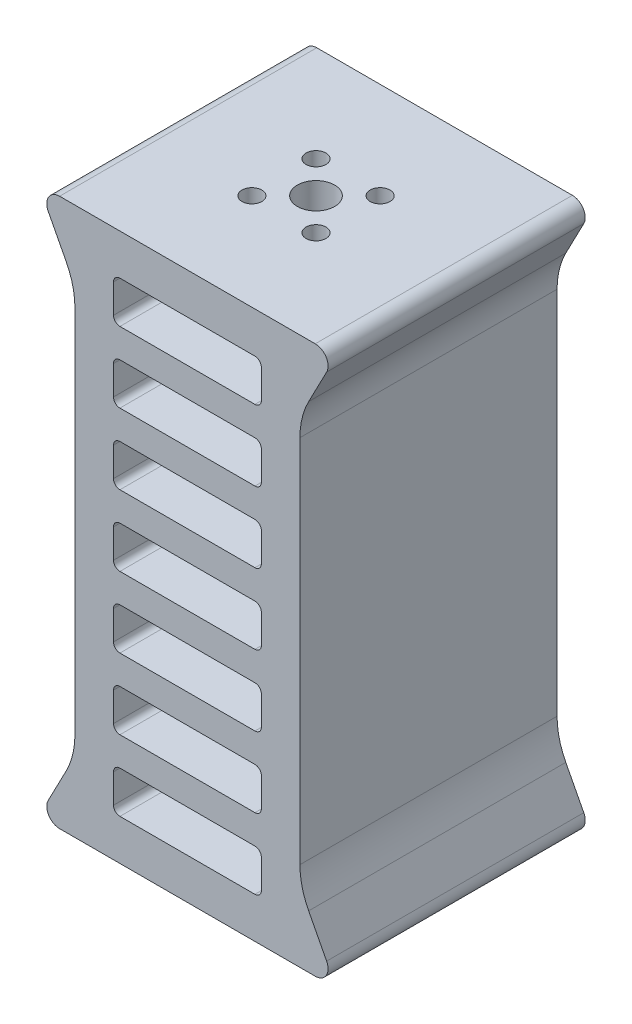
SolidWorks part; units mm, degrees
ref_plane "Front Plane" through (0, 0, 0) normal (0, 0, 1) x (1, 0, 0)
ref_plane "Top Plane" through (0, 0, 0) normal (0, 1, 0) x (1, 0, 0)
ref_plane "Right Plane" through (0, 0, 0) normal (1, 0, 0) x (0, 0, -1)
sketch "Sketch1" plane through (0, 0, 0) normal (0, 0, 1) x (1, 0, 0)
  line L1 (-15.5616, 7.5568) -> (19.4384, 7.5568)
  line L2 (-15.5616, 7.5568) -> (-15.5616, -77.6432)
  line L3 (-15.5616, -77.6432) -> (19.4384, -77.6432)
  line L4 (19.4384, 7.5568) -> (19.4384, -77.6432)
extrude "Boss-Extrude1" add sketch "Sketch1" along normal blind 20 and the other way blind 20
sketch "Sketch2" plane through (0, 0, 20) normal (0, 0, 1) x (1, 0, 0)
  line L0 (-9.5616, -10.7932) -> (-9.5616, -15.2932)
  line L1 (-8.5616, -9.7932) -> (12.4384, -9.7932)
  line L2 (13.4384, -10.7932) -> (13.4384, -15.2932)
  line L3 (-8.5616, -16.2932) -> (12.4384, -16.2932)
  line L4 (-9.5616, -21.7932) -> (-9.5616, -26.2932)
  line L5 (-8.5616, 1.2068) -> (12.4384, 1.2068)
  line L6 (-9.5616, 0.2068) -> (-9.5616, -4.2932)
  line L7 (-8.5616, -5.2932) -> (12.4384, -5.2932)
  line L16 (13.4384, 0.2068) -> (13.4384, -4.2932)
  line L17 (-8.5616, -20.7932) -> (12.4384, -20.7932)
  line L18 (13.4384, -21.7932) -> (13.4384, -26.2932)
  line L19 (-8.5616, -27.2932) -> (12.4384, -27.2932)
  line L20 (-9.5616, -32.7932) -> (-9.5616, -37.2932)
  line L21 (-8.5616, -31.7932) -> (12.4384, -31.7932)
  line L22 (13.4384, -32.7932) -> (13.4384, -37.2932)
  line L23 (-8.5616, -38.2932) -> (12.4384, -38.2932)
  line L24 (-9.5616, -43.7932) -> (-9.5616, -48.2932)
  line L25 (-8.5616, -42.7932) -> (12.4384, -42.7932)
  line L26 (13.4384, -43.7932) -> (13.4384, -48.2932)
  line L27 (-8.5616, -49.2932) -> (12.4384, -49.2932)
  line L28 (-9.5616, -54.7932) -> (-9.5616, -59.2932)
  line L29 (-8.5616, -53.7932) -> (12.4384, -53.7932)
  line L30 (13.4384, -54.7932) -> (13.4384, -59.2932)
  line L31 (-8.5616, -60.2932) -> (12.4384, -60.2932)
  line L32 (-9.5616, -65.7932) -> (-9.5616, -70.2932)
  line L33 (-8.5616, -64.7932) -> (12.4384, -64.7932)
  line L34 (13.4384, -65.7932) -> (13.4384, -70.2932)
  line L35 (-8.5616, -71.2932) -> (12.4384, -71.2932)
  arc A0 (-9.5616, -70.2932) -> (-8.5616, -71.2932) centre (-8.5616, -70.2932) ccw
  arc A1 (13.4384, -70.2932) -> (12.4384, -71.2932) centre (12.4384, -70.2932) cw
  arc A2 (12.4384, -64.7932) -> (13.4384, -65.7932) centre (12.4384, -65.7932) cw
  arc A3 (13.4384, -59.2932) -> (12.4384, -60.2932) centre (12.4384, -59.2932) cw
  arc A4 (-9.5616, -59.2932) -> (-8.5616, -60.2932) centre (-8.5616, -59.2932) ccw
  arc A5 (-9.5616, -65.7932) -> (-8.5616, -64.7932) centre (-8.5616, -65.7932) cw
  arc A6 (-9.5616, -54.7932) -> (-8.5616, -53.7932) centre (-8.5616, -54.7932) cw
  arc A7 (12.4384, -53.7932) -> (13.4384, -54.7932) centre (12.4384, -54.7932) cw
  arc A8 (13.4384, -48.2932) -> (12.4384, -49.2932) centre (12.4384, -48.2932) cw
  arc A9 (-9.5616, -48.2932) -> (-8.5616, -49.2932) centre (-8.5616, -48.2932) ccw
  arc A10 (-9.5616, -43.7932) -> (-8.5616, -42.7932) centre (-8.5616, -43.7932) cw
  arc A11 (12.4384, -42.7932) -> (13.4384, -43.7932) centre (12.4384, -43.7932) cw
  arc A12 (12.4384, -31.7932) -> (13.4384, -32.7932) centre (12.4384, -32.7932) cw
  arc A13 (13.4384, -37.2932) -> (12.4384, -38.2932) centre (12.4384, -37.2932) cw
  arc A14 (-9.5616, -37.2932) -> (-8.5616, -38.2932) centre (-8.5616, -37.2932) ccw
  arc A15 (-9.5616, -32.7932) -> (-8.5616, -31.7932) centre (-8.5616, -32.7932) cw
  arc A16 (-9.5616, -21.7932) -> (-8.5616, -20.7932) centre (-8.5616, -21.7932) cw
  arc A17 (-9.5616, -26.2932) -> (-8.5616, -27.2932) centre (-8.5616, -26.2932) ccw
  arc A18 (13.4384, -26.2932) -> (12.4384, -27.2932) centre (12.4384, -26.2932) cw
  arc A19 (12.4384, -20.7932) -> (13.4384, -21.7932) centre (12.4384, -21.7932) cw
  arc A20 (12.4384, -9.7932) -> (13.4384, -10.7932) centre (12.4384, -10.7932) cw
  arc A21 (13.4384, -15.2932) -> (12.4384, -16.2932) centre (12.4384, -15.2932) cw
  arc A22 (-9.5616, -15.2932) -> (-8.5616, -16.2932) centre (-8.5616, -15.2932) ccw
  arc A23 (-9.5616, -10.7932) -> (-8.5616, -9.7932) centre (-8.5616, -10.7932) cw
  arc A24 (12.4384, 1.2068) -> (13.4384, 0.2068) centre (12.4384, 0.2068) cw
  arc A25 (12.4384, -5.2932) -> (13.4384, -4.2932) centre (12.4384, -4.2932) ccw
  arc A26 (-9.5616, -4.2932) -> (-8.5616, -5.2932) centre (-8.5616, -4.2932) ccw
  arc A27 (-8.5616, 1.2068) -> (-9.5616, 0.2068) centre (-8.5616, 0.2068) ccw
  dimension "D1" = 1
  dimension "D2" = 7
extrude "Cut-Extrude2" cut sketch "Sketch2" against normal up to next
ref_plane "Plane1" through (0, 0, 6) normal (0, 0, 1) x (1, 0, 0)
sketch "Sketch4" plane through (-15.5616, 0, 0) normal (-1, 0, 0) x (0, 0, 1)
  line L0 (20, 7.5568) -> (20, -77.6432) construction
  point P0 (20, -35.0432)
ref_plane "Plane2" through (0, -35.0432, 0) normal (0, 1, 0) x (1, 0, 0)
sketch "Sketch5" plane through (0, 7.5568, 0) normal (0, 1, 0) x (1, 0, 0)
  circle A0 centre (-3.0467, 4.9851) radius 1.55
  circle A1 centre (1.9384, 0) radius 2.9
  circle A2 centre (6.9235, 4.9851) radius 1.55
  circle A3 centre (6.9235, -4.9851) radius 1.55
  circle A4 centre (-3.0467, -4.9851) radius 1.55
  point P9 (1.9384, 0)
  dimension "D2" = 3.1
  dimension "D1" = 4
extrude "Cut-Extrude3" cut sketch "Sketch5" against normal blind 8
sketch "Sketch6" plane through (0, 0, 20) normal (0, 0, 1) x (1, 0, 0)
  line L0 (-15.5616, 7.5568) -> (-15.5616, -77.6432) construction
  point P0 (-15.5616, -35.0432)
ref_plane "Plane3" through (0, -35.0432, 0) normal (0, 1, 0) x (1, 0, 0)
mirror "Mirror3" about plane through (0, -35.0432, 0) normal (0, 1, 0) of "Cut-Extrude3"
sketch "Sketch7" plane through (0, 0, -20) normal (0, 0, -1) x (-1, 0, 0)
  line L0 (-19.4384, 7.5568) -> (-21.8183, 7.5568)
  line L1 (-23.5923, 4.6332) -> (-20.7946, -0.7405)
  line L2 (-19.4384, -77.6432) -> (-19.4384, 7.5568) construction
  line L3 (-19.4384, -6.282) -> (-19.4384, 7.5568)
  line L4 (15.5616, -77.6432) -> (17.9415, -77.6432)
  line L7 (-19.4384, -63.8043) -> (-19.4384, -77.6432)
  line L8 (-23.5923, -74.7196) -> (-20.7946, -69.3459)
  line L9 (-19.4384, -77.6432) -> (-21.8183, -77.6432)
  line L10 (19.7155, -74.7196) -> (16.9177, -69.3459)
  line L11 (15.5616, -63.8043) -> (15.5616, -77.6432)
  line L12 (15.5616, -6.282) -> (15.5616, 7.5568)
  line L13 (19.7155, 4.6332) -> (16.9177, -0.7405)
  line L14 (15.5616, 7.5568) -> (17.9415, 7.5568)
  arc A0 (-21.8183, 7.5568) -> (-23.5923, 4.6332) centre (-21.8183, 5.5568) ccw
  arc A1 (-20.7946, -0.7405) -> (-19.4384, -6.282) centre (-31.4384, -6.282) cw
  arc A2 (-20.7946, -69.3459) -> (-19.4384, -63.8043) centre (-31.4384, -63.8043) ccw
  arc A3 (-21.8183, -77.6432) -> (-23.5923, -74.7196) centre (-21.8183, -75.6432) cw
  arc A4 (17.9415, -77.6432) -> (19.7155, -74.7196) centre (17.9415, -75.6432) ccw
  arc A5 (16.9177, -69.3459) -> (15.5616, -63.8043) centre (27.5616, -63.8043) cw
  arc A6 (16.9177, -0.7405) -> (15.5616, -6.282) centre (27.5616, -6.282) ccw
  arc A7 (17.9415, 7.5568) -> (19.7155, 4.6332) centre (17.9415, 5.5568) cw
  point P11 (-19.4384, -3.3453)
  point P24 (-19.4384, -66.7411)
  point P37 (15.5616, -66.7411)
  point P38 (15.5616, -3.3453)
  dimension "D1" = 2
  dimension "D2" = 12
extrude "Boss-Extrude2" add sketch "Sketch7" against normal up to surface (40 mm away) up to face at (1.9384, -68.0432, 20)
